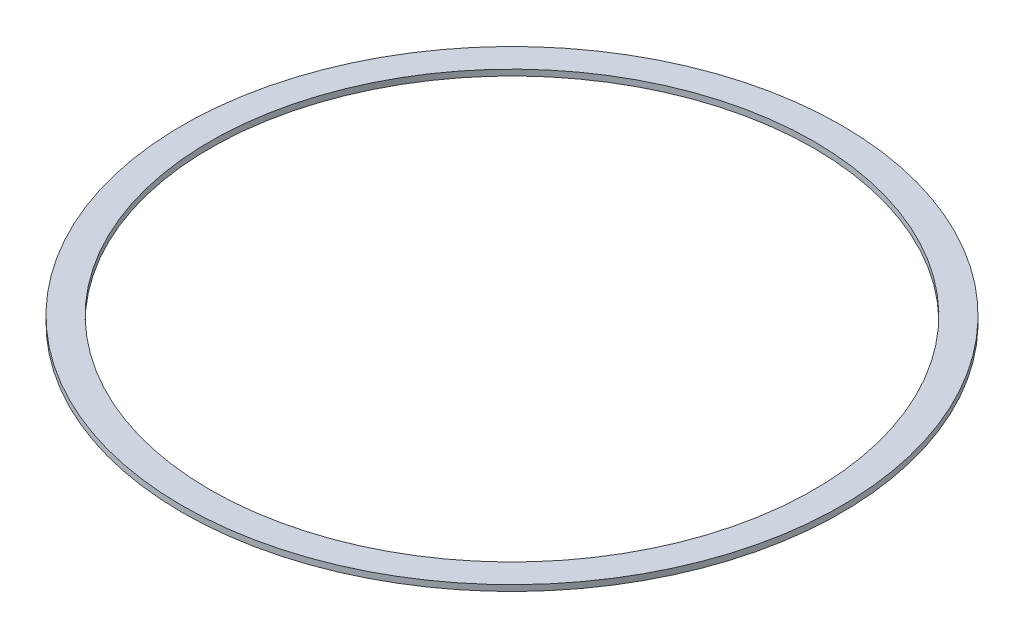
SolidWorks part; units mm, degrees
material "Медь"
ref_plane "Спереди" through (0, 0, 0) normal (0, 0, 1) x (1, 0, 0)
ref_plane "Сверху" through (0, 0, 0) normal (0, 1, 0) x (1, 0, 0)
ref_plane "Справа" through (0, 0, 0) normal (1, 0, 0) x (0, 0, -1)
ref_axis "Ось1" through (0, 0, 0) along (0, 1, 0)
sketch "Эскиз1" plane through (0, 0, 0) normal (0, 0, 1) x (1, 0, 0)
  line L0 (0, 12.9616) -> (0, -13.6191) construction
  line L1 (0, 0) -> (101.69, 0) construction
  line L3 (101.69, 1) -> (111.035, 1)
  line L4 (101.69, 1) -> (101.69, -1)
  line L5 (101.69, -1) -> (111.035, -1)
  line L6 (111.035, 1) -> (111.035, -1)
  point P9 (0, 12.9616)
  point P10 (0, -13.6191)
  dimension "D1" = 203.38
  dimension "D2" = 222.07
  dimension "D3" = 2
revolve "Повернуть1" add sketch "Эскиз1" angle 360 about L0
